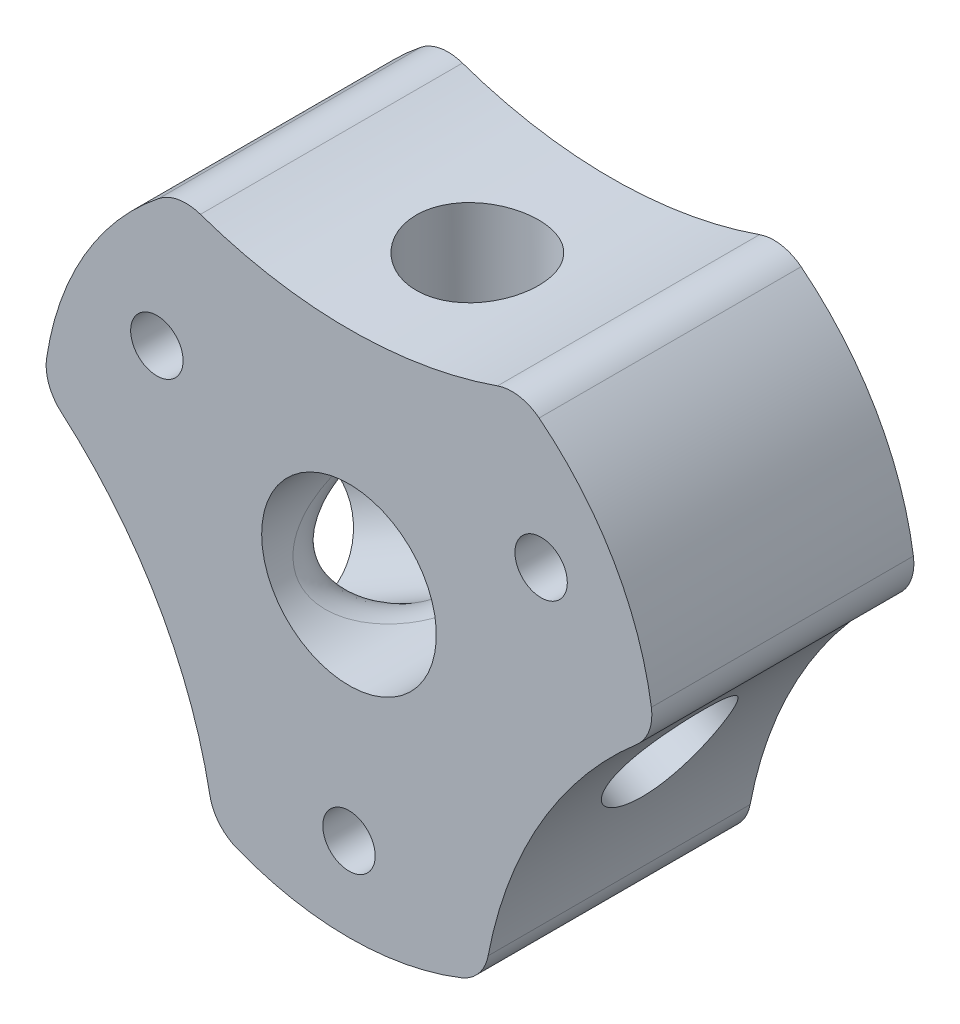
SolidWorks part; units mm, degrees
ref_plane "Front" through (0, 0, 0) normal (0, 0, 1) x (1, 0, 0)
ref_plane "Top" through (0, 0, 0) normal (0, 1, 0) x (1, 0, 0)
ref_plane "Right" through (0, 0, 0) normal (1, 0, 0) x (0, 0, -1)
sketch "Szkic1" plane through (0, 0, 0) normal (0, 0, 1) x (1, 0, 0)
  line L0 (0, 0) -> (0, -25.4) construction
  circle A0 centre (0, 0) radius 25.4
  circle A1 centre (0, -25.4) radius 3
  circle A2 centre (-21.997, 12.7) radius 3
  circle A3 centre (21.997, 12.7) radius 3
  circle A4 centre (0, 0) radius 35
  dimension "D1" = 50.8
  dimension "D4" = 6
  dimension "D5" = 70
  dimension "D3" = 25.4
  dimension "D2" = 3
extrude "Dodanie-wyciągnięcie1" add sketch "Szkic1" along normal blind 30 contours A4 A3 A0 A1 A2 | A3 A0 A2 A1 region at (0, 0, 0) region at (-34.0101, 0, 0)
sketch "Szkic2" plane through (0, 0, 0) normal (0, 0, -1) x (-1, 0, 0)
  line L0 (0, 0) -> (19.4145, 29.1218) construction
  arc A0 (-19.4145, 29.1218) -> (19.4145, 29.1218) centre (0, 76.903) ccw
  circle A1 centre (0, 0) radius 35 construction
  arc A2 (-19.4145, 29.1218) -> (19.4145, 29.1218) centre (0, 0) cw
  arc A3 (34.9274, 2.2526) -> (15.5129, -31.3743) centre (0, 0) cw
  arc A4 (34.9274, 2.2526) -> (15.5129, -31.3743) centre (66.5999, -38.4515) ccw
  arc A5 (-15.5129, -31.3743) -> (-34.9274, 2.2526) centre (0, 0) cw
  arc A6 (-15.5129, -31.3743) -> (-34.9274, 2.2526) centre (-66.5999, -38.4515) ccw
  dimension "D2" = 35
  dimension "D1" = 3
extrude "Wytnij-wyciągnięcie1" cut sketch "Szkic2" against normal through all
fillet "Zaokrąglenie1" radius 5 6 edges at (19.4145, 29.1218, 15) (-19.4145, 29.1218, 15) (-34.9274, 2.2526, 15) (-15.5129, -31.3743, 15) (15.5129, -31.3743, 15) (34.9274, 2.2526, 15)
sketch "Szkic3" plane through (0, 0, 0) normal (0, 0, -1) x (-1, 0, 0)
  circle A0 centre (0, 0) radius 10
  dimension "D1" = 20
extrude "Wytnij-wyciągnięcie2" cut sketch "Szkic3" against normal through all
ref_plane "Płaszczyzna1" through (0, 0, 0) normal (0, 1, 0) x (1, 0, 0)
sketch "Szkic4" plane through (0, 0, 0) normal (0, 1, 0) x (1, 0, 0)
  circle A0 centre (0, -15.3006) radius 7
  dimension "D1" = 14
extrude "Wytnij-wyciągnięcie3" cut sketch "Szkic4" along normal blind 30
pattern_circular "Szyk kołowy1" count 3 over 360 about axis through (0, 0, 30) along (0, 0, -1) of "Wytnij-wyciągnięcie3"
fillet "Zaokrąglenie2" radius 5 3 edges at (-5.6135, -8.2758, 9.8245) (-1.045, 9.9452, 22.2222) (9.7039, 2.4153, 14.4145)
